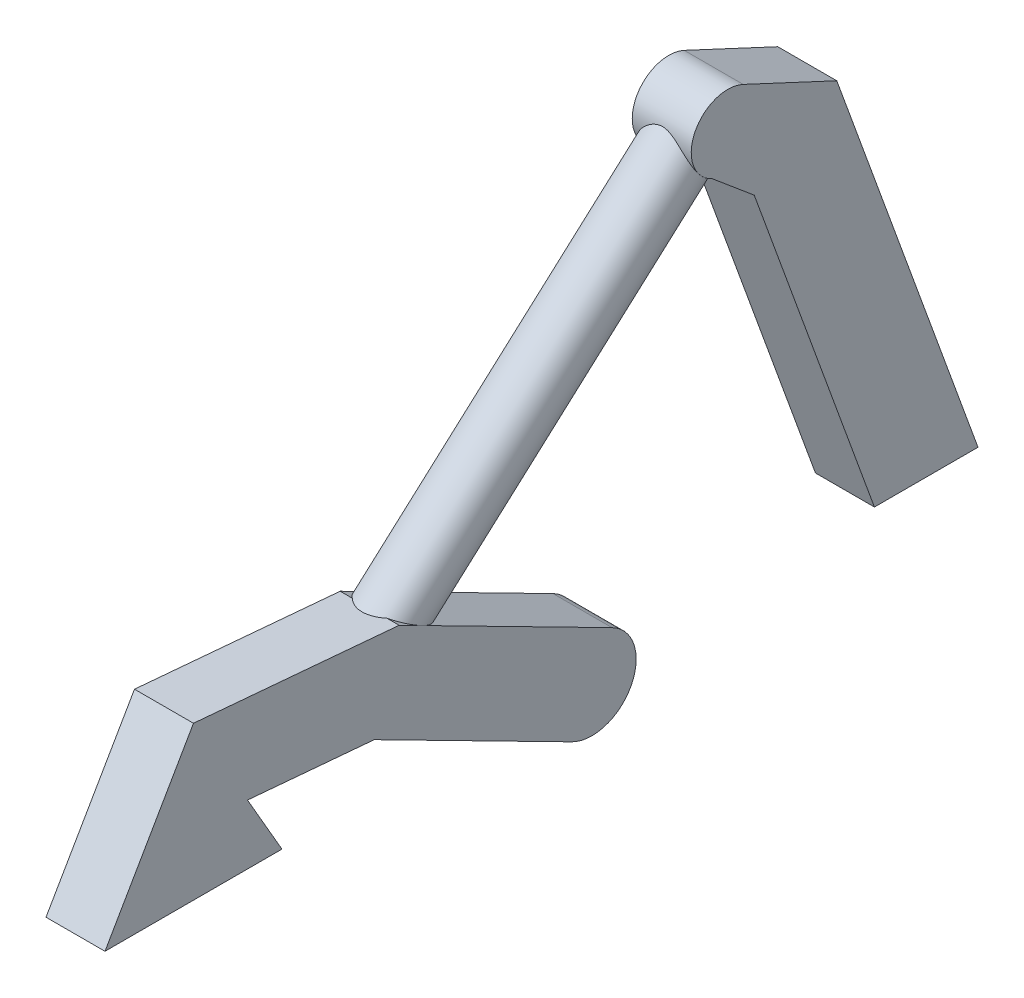
SolidWorks part; units mm, degrees
ref_plane "前视基准面" through (0, 0, 0) normal (0, 0, 1) x (1, 0, 0)
ref_plane "上视基准面" through (0, 0, 0) normal (0, 1, 0) x (1, 0, 0)
ref_plane "右视基准面" through (0, 0, 0) normal (1, 0, 0) x (0, 0, -1)
other "Configuration Table"
sketch "草图1" plane through (0, 0, 0) normal (1, 0, 0) x (0, 0, -1)
  line L0 (0, 0) -> (-72.1351, 0) construction
  line L1 (-95, 58.3581) -> (-95, -58.3581) construction
  line L6 (131, 0) -> (83.1172, 131.557)
  line L7 (95.8821, 0) -> (55.1316, 111.9612)
  line L9 (95, 58.3581) -> (95, -58.3581) construction
  line L11 (131, 0) -> (95.8821, 0)
  line L12 (99.9901, -11.2867) -> (52.1073, 120.2703) construction
  line L13 (83.1172, 131.557) -> (51.3964, 146.3486)
  line L14 (55.1316, 111.9612) -> (40.9214, 123.885)
  line L15 (83.1172, 131.557) -> (55.1316, 111.9612) construction
  line L16 (51.3964, 146.3486) -> (40.9214, 123.885) construction
  line L17 (-165, 0) -> (-135, 51.9615)
  line L18 (-105, 0) -> (-116.6884, 20.2449)
  line L19 (-135, 51.9615) -> (-65.2664, 45.8606)
  line L20 (-73.6903, 16.483) -> (-116.6884, 20.2449)
  line L21 (-65.2664, 45.8606) -> (6.9052, 9.0874)
  line L22 (-65.2664, 45.8606) -> (-73.6903, 16.483) construction
  line L23 (-165, 0) -> (-105, 0)
  line L24 (46.1589, 135.1168) -> (-69.4783, 31.1718) construction
  line L25 (-73.6903, 16.483) -> (-6.7146, -17.6428)
  line L26 (6.9052, 9.0874) -> (-6.7146, -17.6428) construction
  line L27 (-137.6147, 22.0757) -> (-73.6903, 16.483) construction
  line L28 (-69.4783, 31.1718) -> (46.1589, 135.1168)
  line L29 (-69.4783, 31.1718) -> (-62.7932, 23.7348)
  line L30 (46.1589, 135.1168) -> (52.844, 127.6797)
  line L31 (-62.7932, 23.7348) -> (52.844, 127.6797)
  arc A0 (51.3964, 146.3486) -> (40.9214, 123.885) centre (46.1589, 135.1168) ccw
  arc A1 (-6.7146, -17.6428) -> (6.9052, 9.0874) centre (0.0953, -4.2777) ccw
  circle A2 centre (-69.4783, 31.1718) radius 15.2808 construction
  point P1 (0, 0)
  dimension "D1" = 190
  dimension "D2" = 95
  dimension "D3" = 70
  dimension "D4" = 140
  dimension "D6" = 36
  dimension "D7" = 135
  dimension "D8" = 150
  dimension "D9" = 35
  dimension "D10" = 75
  dimension "D11" = 70
  dimension "D12" = 60
  dimension "D13" = 60
  dimension "D14" = 55
  dimension "D15" = 60
  dimension "D16" = 70
  dimension "D17" = 158
  dimension "D18" = 10
  dimension "D20" = 10
  dimension "D21" = 81
  dimension "D5" = 33
  dimension "D19" = 30
revolve "旋转1" add sketch "草图1" angle 360 about L24 region at (0, 81.5911, 5.9269) region at (0, 127.6374, -45.1052) region at (0, 33.3591, 59.2991)
extrude "凸台-拉伸1" add sketch "草图1<3>" along normal mid plane 20 contours L13 A0 L28 L30 L31 L14 L7 L11 L6 | L28 A0 L14 L31 L30 | L25 A1 L21 L31 L29 L28 L19 L17 L23 L18 L20 | L29 L31 L21 L28 region at (0, 72.9072, -85.6839) region at (0, 127.6374, -45.1052) region at (0, 18.9733, 77.0831) region at (0, 33.3591, 59.2991)
sketch "草图1<3>" plane through (0, 0, 0) normal (1, 0, 0) x (0, 0, -1) same geometry as "草图1"
